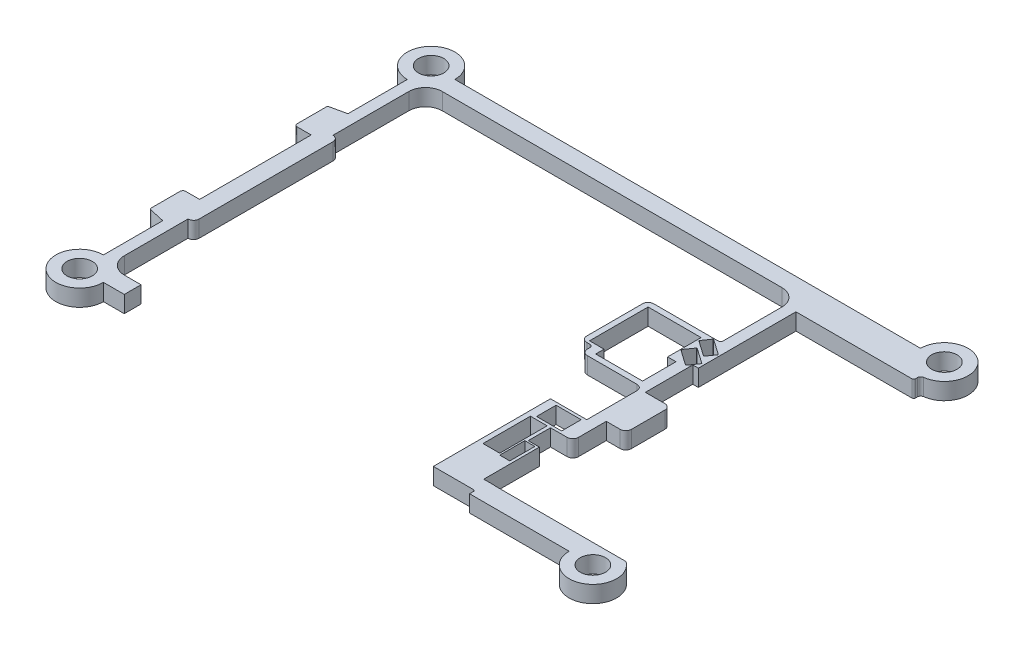
SolidWorks part; units mm, degrees
material "Balsa"
ref_plane "Front Plane" through (0, 0, 0) normal (0, 0, 1) x (1, 0, 0)
ref_plane "Top Plane" through (0, 0, 0) normal (0, 1, 0) x (1, 0, 0)
ref_plane "Right Plane" through (0, 0, 0) normal (1, 0, 0) x (0, 0, -1)
sketch "Sketch1" plane through (0, 0, 0) normal (0, 1, 0) x (1, 0, 0)
  line L0 (46, 0) -> (46, -63) construction
  line L5 (0, -4.265) -> (0, -58.735)
  line L6 (3.2, -3.25) -> (88.8, -3.25) construction
  line L7 (3.2, -3.25) -> (3.2, -59.75) construction
  line L8 (3.2, -59.75) -> (88.8, -59.75) construction
  line L9 (88.8, -3.25) -> (88.8, -59.75) construction
  line L10 (3.2, -3.25) -> (88.8, -59.75) construction
  line L11 (3.2, -59.75) -> (88.8, -3.25) construction
  line L12 (4.265, 0) -> (87.735, 0)
  line L14 (92, -4.265) -> (92, -58.735)
  line L15 (4.265, -63) -> (87.735, -63)
  circle A0 centre (0, 0) radius 2.265
  circle A1 centre (92, 0) radius 2.265
  circle A2 centre (92, -63) radius 2.265
  circle A3 centre (0, -63) radius 2.265
  arc A4 (4.265, 0) -> (0, -4.265) centre (0, 0) ccw
  arc A5 (92, -4.265) -> (87.735, 0) centre (92, 0) ccw
  arc A6 (87.735, -63) -> (92, -58.735) centre (92, -63) ccw
  arc A7 (0, -58.735) -> (4.265, -63) centre (0, -63) ccw
  point P7 (46, -31.5)
  dimension "D5" = 4.53
  dimension "D6" = 2
  dimension "D1" = 92
  dimension "D2" = 63
  dimension "D3" = 85.6
  dimension "D4" = 56.5
extrude "Boss-Extrude1" add sketch "Sketch1" along normal blind 3
sketch "Sketch2" plane through (0, 3, 0) normal (0, 1, 0) x (1, 0, 0)
  line L0 (0, -31.5) -> (92, -31.5) construction
  line L1 (0, -4.265) -> (0, -58.735) construction
  line L2 (92, -58.735) -> (92, -4.265) construction
  line L4 (0, -21.5) -> (6.5, -21.5)
  line L5 (0, -21.5) -> (0, -41.5)
  line L6 (0, -41.5) -> (6.5, -41.5)
  line L7 (6.5, -21.5) -> (6.5, -41.5)
  point P11 (0, -31.5)
  dimension "D1" = 20
  dimension "D2" = 6.5
extrude "Cut-Extrude1" cut sketch "Sketch2" against normal blind 3
sketch "Sketch3" plane through (0, 3, 0) normal (0, 1, 0) x (1, 0, 0)
  line L0 (-2.7, -15.5) -> (0, -14.9)
  line L1 (0, -21.5) -> (-2.5, -21.5)
  line L2 (0, -21.5) -> (0, -14.9)
  line L4 (-3, -21) -> (-3, -15.8)
  line L5 (6.5, -31.5) -> (-11.9929, -31.5) construction
  line L6 (6.5, -41.5) -> (6.5, -21.5) construction
  line L7 (-3, -42) -> (-3, -47.2)
  line L8 (0, -41.5) -> (-2.5, -41.5)
  line L9 (0, -41.5) -> (0, -48.1)
  line L10 (-2.7, -47.5) -> (0, -48.1)
  arc A0 (-2.5, -21.5) -> (-3, -21) centre (-2.5, -21) cw
  arc A1 (-3, -15.8) -> (-2.7, -15.5) centre (-2.7, -15.8) cw
  arc A2 (-3, -47.2) -> (-2.7, -47.5) centre (-2.7, -47.2) ccw
  arc A3 (-2.5, -41.5) -> (-3, -42) centre (-2.5, -42) ccw
  point P7 (-3, -21.5)
  point P10 (-3, -15.5)
  dimension "D3" = 0.5
  dimension "D4" = 0.3
  dimension "D1" = 3
  dimension "D2" = 6
  dimension "D5" = 6.6
extrude "Boss-Extrude2" add sketch "Sketch3" against normal blind 3
sketch "Sketch5" plane through (0, 3, 0) normal (0, 1, 0) x (1, 0, 0)
  line L2 (0, -16.9) -> (0, -48.265) construction
  line L3 (0, -45.5825) -> (3, -45.5825)
  line L4 (0, -45.5825) -> (0, -19.5825)
  line L5 (0, -19.5825) -> (3, -19.5825)
  line L6 (3, -45.5825) -> (3, -19.5825)
  point P1 (0, -32.5825)
  point P14 (0, -32.5825)
  dimension "D1" = 26
  dimension "D2" = 3
  dimension "D3" = 2
  dimension "D4" = 44
sketch "Sketch6" plane through (0, 3, 0) normal (0, 1, 0) x (1, 0, 0)
  line L0 (0, -4.265) -> (0, -14.9) construction
  line L1 (5, -3) -> (65.9, -3)
  line L2 (2, -6) -> (2, -57)
  line L3 (5, -60) -> (65.9, -60)
  line L4 (68.9, -6) -> (68.9, -57)
  line L5 (2, -3) -> (68.9, -60) construction
  line L6 (2, -60) -> (68.9, -3) construction
  line L7 (87.735, 0) -> (4.265, 0) construction
  line L8 (4.265, -63) -> (87.735, -63) construction
  arc A0 (2, -57) -> (5, -60) centre (5, -57) ccw
  arc A1 (65.9, -60) -> (68.9, -57) centre (65.9, -57) ccw
  arc A2 (68.9, -6) -> (65.9, -3) centre (65.9, -6) ccw
  arc A3 (2, -6) -> (5, -3) centre (5, -6) cw
  point P0 (35.45, -31.5)
  dimension "D5" = 3
  dimension "D1" = 2
  dimension "D2" = 3
  dimension "D3" = 3
  dimension "D4" = 68.9
extrude "Cut-Extrude2" cut sketch "Sketch6" against normal blind 3
extrude "Boss-Extrude6" add sketch "Sketch5" against normal blind 3
fillet "Fillet1" radius 1 2 edges at (3, 1.5, 45.5825) (3, 1.5, 19.5825)
sketch "Sketch9" plane through (0, 3, 0) normal (0, 1, 0) x (1, 0, 0)
  line L0 (5, -60) -> (65.9, -60) construction
  line L1 (8, -60) -> (65, -60)
  line L2 (8, -60) -> (8, -63)
  line L3 (8, -63) -> (65, -63)
  line L4 (65, -60) -> (65, -63)
  line L5 (4.265, -63) -> (87.735, -63) construction
  line L6 (2, -45.5825) -> (2, -57) construction
  dimension "D1" = 6
extrude "Cut-Extrude4" cut sketch "Sketch9" against normal blind 3
sketch "Sketch11" plane through (0, 3, 0) normal (0, 1, 0) x (1, 0, 0)
  line L0 (92, -58.735) -> (92, -4.265) construction
  line L1 (92, -5.5) -> (70.9, -5.5)
  line L2 (92, -5.5) -> (92, -59.5)
  line L3 (92, -59.5) -> (70.9, -59.5)
  line L4 (70.9, -5.5) -> (70.9, -59.5)
  line L5 (87.735, 0) -> (4.265, 0) construction
  line L6 (68.9, -57) -> (68.9, -6) construction
  line L7 (65, -63) -> (87.735, -63) construction
  dimension "D1" = 5.5
  dimension "D2" = 2
  dimension "D3" = 3.5
extrude "Cut-Extrude6" cut sketch "Sketch11" against normal blind 3
sketch "Sketch12" plane through (0, 3, 0) normal (0, 1, 0) x (1, 0, 0)
  line L1 (92, -59.5) -> (97.6068, -59.5)
  line L2 (92, -59.5) -> (92, -56.3336)
  line L3 (92, -56.3336) -> (97.6068, -56.3336)
  line L4 (97.6068, -59.5) -> (97.6068, -56.3336)
extrude "Cut-Extrude7" cut sketch "Sketch12" against normal blind 3
sketch "Sketch13" plane through (0, 3, 0) normal (0, 1, 0) x (1, 0, 0)
  line L0 (92, -5.5) -> (92, -4.265)
  line L1 (95.7069, -2.1093) -> (95.7069, -5.5)
  line L2 (92, -5.5) -> (95.7069, -5.5)
  arc A0 (92, -4.265) -> (95.7069, -2.1093) centre (92, 0) ccw
  arc A1 (92, -4.265) -> (87.735, 0) centre (92, 0) ccw construction
extrude "Boss-Extrude7" [suppressed] add sketch "Sketch13" against normal blind 3
sketch "Sketch14" plane through (0, 3, 0) normal (0, 1, 0) x (1, 0, 0)
  line L0 (68.9, -57) -> (68.9, -6) construction
  line L1 (68.9, -17) -> (55.9, -17)
  line L2 (68.9, -17) -> (68.9, -31)
  line L3 (68.9, -31) -> (55.9, -31)
  line L4 (55.9, -17) -> (55.9, -31)
  line L5 (65.9, -3) -> (5, -3) construction
  line L6 (70.9, -5.5) -> (70.9, -59.5) construction
  line L7 (56.9, -18) -> (67.9, -18)
  line L8 (56.9, -18) -> (56.9, -30)
  line L9 (56.9, -30) -> (67.9, -30)
  line L10 (67.9, -18) -> (67.9, -30)
  dimension "D1" = 14
  dimension "D2" = 14
  dimension "D3" = 1
  dimension "D4" = 1
  dimension "D5" = 1
  dimension "D6" = 1
  dimension "D7" = 15
extrude "Boss-Extrude9" add sketch "Sketch14" against normal blind 3
sketch "Sketch15" plane through (0, 3, 0) normal (0, 1, 0) x (1, 0, 0)
  line L0 (70.9, -5.5) -> (70.9, -59.5) construction
  line L1 (70.9, -31.5) -> (69.9, -31.5)
  line L2 (70.9, -31.5) -> (70.9, -23)
  line L3 (70.9, -23) -> (69.9, -23)
  line L4 (69.9, -31.5) -> (69.9, -23)
  dimension "D1" = 17.5
  dimension "D2" = 8.5
  dimension "D3" = 1
extrude "Cut-Extrude8" cut sketch "Sketch15" against normal blind 3
sketch "Sketch16" plane through (0, 3, 0) normal (0, 1, 0) x (1, 0, 0)
  line L0 (68.9, -57) -> (68.9, -31) construction
  line L1 (70.9, -31.5) -> (74.4, -31.5)
  line L2 (70.9, -31.5) -> (70.9, -39.5)
  line L3 (70.9, -39.5) -> (74.4, -39.5)
  line L4 (74.4, -31.5) -> (74.4, -39.5)
  dimension "D1" = 8
  dimension "D2" = 5.5
extrude "Boss-Extrude10" add sketch "Sketch16" against normal blind 3
sketch "Sketch17" plane through (0, 3, 0) normal (0, 1, 0) x (1, 0, 0)
  line L1 (67.9, -18) -> (66.4, -18)
  line L2 (67.9, -18) -> (67.9, -24)
  line L3 (67.9, -24) -> (66.4, -24)
  line L4 (66.4, -18) -> (66.4, -24)
  dimension "D1" = 6
  dimension "D2" = 1.5
extrude "Boss-Extrude11" add sketch "Sketch17" against normal blind 3
sketch "Sketch18" plane through (0, 3, 0) normal (0, 1, 0) x (1, 0, 0)
  line L0 (66.7169, -18.5904) -> (67.692, -17.1978)
  line L1 (67.8313, -17.1733) -> (70.5345, -19.0661)
  line L2 (70.559, -19.2054) -> (69.584, -20.5979)
  line L3 (69.4447, -20.6225) -> (66.7415, -18.7297)
  line L4 (66.5016, -21.6063) -> (67.5914, -20.0499)
  line L5 (67.7307, -20.0254) -> (70.4339, -21.9182)
  line L6 (70.4585, -22.0574) -> (69.3687, -23.6138)
  line L7 (69.2294, -23.6384) -> (66.5262, -21.7456)
  line L8 (66.4, -18) -> (66.4, -24) construction
  arc A0 (66.7415, -18.7297) -> (66.7169, -18.5904) centre (66.7989, -18.6477) cw
  arc A1 (67.692, -17.1978) -> (67.8313, -17.1733) centre (67.7739, -17.2552) cw
  arc A2 (70.559, -19.2054) -> (70.5345, -19.0661) centre (70.4771, -19.148) ccw
  arc A3 (69.584, -20.5979) -> (69.4447, -20.6225) centre (69.5021, -20.5406) cw
  arc A4 (69.3687, -23.6138) -> (69.2294, -23.6384) centre (69.2867, -23.5565) cw
  arc A5 (70.4585, -22.0574) -> (70.4339, -21.9182) centre (70.3765, -22.0001) ccw
  arc A6 (67.5914, -20.0499) -> (67.7307, -20.0254) centre (67.6733, -20.1073) cw
  arc A7 (66.5262, -21.7456) -> (66.5016, -21.6063) centre (66.5835, -21.6637) cw
  point P12 (66.6596, -18.6723)
  point P15 (67.7494, -17.1159)
  point P18 (70.6164, -19.1234)
  point P25 (70.5158, -21.9755)
  point P28 (67.6488, -19.968)
  dimension "D6" = 0.1
  dimension "D1" = 1.9
  dimension "D2" = 3.5
  dimension "D3" = 55
  dimension "D4" = 55
  dimension "D5" = 3.5
  dimension "D7" = 1.9
extrude "Cut-Extrude9" cut sketch "Sketch18" against normal blind 3
sketch "Sketch19" plane through (0, 3, 0) normal (0, 1, 0) x (1, 0, 0)
  line L1 (55.9, -31) -> (58, -31)
  line L2 (55.9, -31) -> (55.9, -29)
  line L3 (55.9, -29) -> (58, -29)
  line L4 (58, -31) -> (58, -29)
  dimension "D1" = 2.1
  dimension "D2" = 2
extrude "Cut-Extrude10" cut sketch "Sketch19" against normal blind 3
sketch "Sketch31" plane through (0, 3, 0) normal (0, 1, 0) x (1, 0, 0)
  line L1 (58, -30) -> (59.5, -30)
  line L2 (58, -30) -> (58, -29)
  line L3 (58, -28.5) -> (59.5, -28.5)
  line L4 (59.5, -30) -> (59.5, -28.5)
  line L5 (56.9, -29) -> (58, -29)
  line L6 (56.9, -29) -> (56.9, -28.5)
  line L7 (56.9, -28.5) -> (58, -28.5)
  dimension "D1" = 1.5
  dimension "D2" = 2.5
extrude "Boss-Extrude16" add sketch "Sketch31" against normal blind 3
fillet "Fillet2" radius 1 4 edges at (68.9, 1.5, 31) (58, 1.5, 31) (55.9, 1.5, 29) (55.9, 1.5, 17)
fillet "Fillet3" radius 0.5 1 edges at (68.9, 1.5, 17)
fillet "Fillet4" radius 0.5 1 edges at (58, 1.5, 29)
fillet "Fillet6" radius 1 2 edges at (74.4, 1.5, 39.5) (74.4, 1.5, 31.5)
sketch "Sketch21" plane through (0, 3, 0) normal (0, 1, 0) x (1, 0, 0)
  line L0 (74.4, -38.5) -> (74.4, -32.5) construction
  line L1 (70.4, -41) -> (62.4, -41)
  line L2 (70.4, -41) -> (70.4, -63)
  line L3 (70.4, -63) -> (62.4, -63)
  line L4 (62.4, -41) -> (62.4, -63)
  line L5 (59, -31) -> (67.9, -31) construction
  line L6 (65, -63) -> (87.735, -63) construction
  dimension "D1" = 4
  dimension "D2" = 10
  dimension "D3" = 12
extrude "Boss-Extrude13" add sketch "Sketch21" against normal blind 3
sketch "Sketch24" plane through (0, 3, 0) normal (0, 1, 0) x (1, 0, 0)
  line L13 (68.14, -45.5) -> (72.14, -45.5)
  line L18 (68.14, -45.5) -> (68.14, -51.9336)
  line L19 (68.14, -51.9336) -> (72.14, -51.9336)
  line L20 (72.14, -45.5) -> (72.14, -51.9336)
  line L22 (68.9, -41) -> (62.4, -41) construction
  line L23 (62.4, -41) -> (62.4, -63) construction
  dimension "D1" = 4
  dimension "D2" = 6.4336
  dimension "D3" = 4.5
  dimension "D4" = 5.74
extrude "Cut-Extrude12" cut sketch "Sketch24" against normal blind 3
fillet "Fillet9" radius 1 1 edges at (70.9, 1.5, 45.5)
sketch "Sketch25" plane through (0, 3, 0) normal (0, 1, 0) x (1, 0, 0)
  line L0 (68.9, -41) -> (62.4, -41) construction
  line L1 (63.9, -41.5) -> (68.4, -41.5)
  line L2 (63.9, -41.5) -> (63.9, -45)
  line L3 (63.9, -45) -> (68.4, -45)
  line L4 (68.4, -41.5) -> (68.4, -45)
  line L5 (62.4, -41) -> (62.4, -63) construction
  line L6 (70.4, -41) -> (70.4, -44.4752) construction
  line L7 (70.9, -39.5) -> (70.9, -44.5) construction
  line L8 (66.9, -45.5) -> (70.9, -45.5)
  line L9 (66.9, -45.5) -> (66.9, -49.5)
  line L10 (66.9, -49.5) -> (70.9, -49.5)
  line L11 (70.9, -45.5) -> (70.9, -49.5)
  dimension "D1" = 4.5
  dimension "D2" = 3.5
  dimension "D3" = 0.5
  dimension "D4" = 1.5
  dimension "D5" = 2
  dimension "D6" = 4
  dimension "D7" = 4
  dimension "D8" = 0.5
  dimension "D9" = 4
extrude "Cut-Extrude14" cut sketch "Sketch25" against normal blind 3
sketch "Sketch26" plane through (0, 3, 0) normal (0, 1, 0) x (1, 0, 0)
  line L1 (66.9, -49.5) -> (70.9, -49.5)
  line L2 (66.9, -49.5) -> (66.9, -51.9336)
  line L3 (66.9, -51.9336) -> (70.9, -51.9336)
  line L4 (70.9, -49.5) -> (70.9, -51.9336)
extrude "Boss-Extrude15" add sketch "Sketch26" against normal blind 3
sketch "Sketch27" plane through (0, 3, 0) normal (0, 1, 0) x (1, 0, 0)
  line L0 (62.4, -41) -> (62.4, -63) construction
  line L1 (63.3, -45.5) -> (66.3, -45.5)
  line L2 (63.3, -45.5) -> (63.3, -54)
  line L3 (63.3, -54) -> (66.3, -54)
  line L4 (66.3, -45.5) -> (66.3, -54)
  line L5 (63.9, -45) -> (68.4, -45) construction
  point P6 (62.4, -52)
  dimension "D1" = 8.5
  dimension "D2" = 3
  dimension "D3" = 0.9
  dimension "D4" = 0.5
extrude "Cut-Extrude15" cut sketch "Sketch27" against normal blind 3
sketch "Sketch28" plane through (0, 3, 0) normal (0, 1, 0) x (1, 0, 0)
  line L1 (66.6, -49.8) -> (68.4, -49.8)
  line L2 (66.6, -49.8) -> (66.6, -54.3)
  line L3 (66.6, -54.3) -> (68.4, -54.3)
  line L4 (68.4, -49.8) -> (68.4, -54.3)
  line L5 (66.3, -54) -> (66.3, -45.5) construction
  line L6 (66.9, -49.5) -> (70.9, -49.5) construction
  point P10 (67.5, -49.8)
  dimension "D1" = 4.5
  dimension "D2" = 1.8
  dimension "D3" = 0.3
  dimension "D4" = 0.3
extrude "Cut-Extrude16" cut sketch "Sketch28" against normal blind 3
sketch "Sketch29" plane through (0, 3, 0) normal (0, 1, 0) x (1, 0, 0)
  line L0 (68.4, -54.3) -> (68.4, -49.8) construction
  line L1 (70.9, -49.5) -> (68.9026, -49.5)
  line L2 (70.9, -49.5) -> (70.9, -59.4683)
  line L3 (70.9, -59.4683) -> (68.9026, -59.4683)
  line L4 (68.9026, -49.5) -> (68.9026, -59.4683)
  dimension "D1" = 0.5026
extrude "Cut-Extrude17" cut sketch "Sketch29" against normal blind 3
sketch "Sketch30" plane through (0, 3, 0) normal (0, 1, 0) x (1, 0, 0)
  line L1 (62.4, -63) -> (69.9, -63)
  line L2 (62.4, -63) -> (62.4, -62)
  line L3 (62.4, -62) -> (69.9, -62)
  line L4 (69.9, -63) -> (69.9, -62)
  dimension "D1" = 1
  dimension "D2" = 7.5
extrude "Cut-Extrude18" cut sketch "Sketch30" against normal blind 3
fillet "Fillet10" [suppressed] radius 0.6
fillet "Fillet11" radius 0.3 1 edges at (69.9, 1.5, 62)
fillet "Fillet12" radius 0.6 1 edges at (92, 1.5, 4.265)
fillet "Fillet13" radius 0.3 1 edges at (92, 1.5, 5.5)
